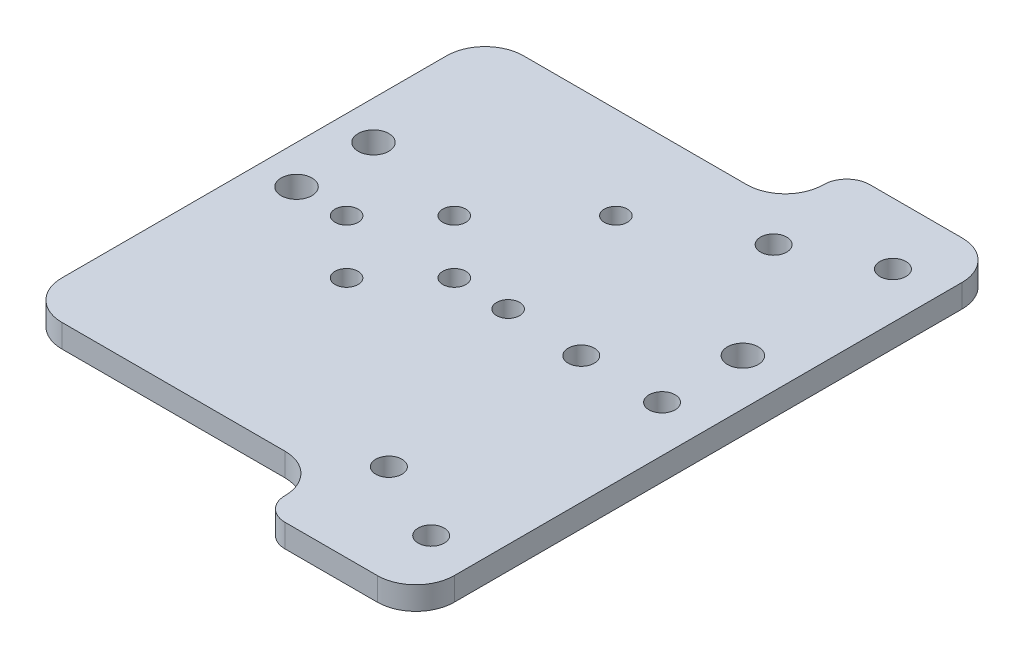
SolidWorks part; units mm, degrees
ref_plane "前视基准面" through (0, 0, 0) normal (0, 0, 1) x (1, 0, 0)
ref_plane "上视基准面" through (0, 0, 0) normal (0, 1, 0) x (1, 0, 0)
ref_plane "右视基准面" through (0, 0, 0) normal (1, 0, 0) x (0, 0, -1)
sketch "草图1" plane through (0, 0, 0) normal (0, 1, 0) x (1, 0, 0)
  line L0 (42.5, 25) -> (42.5, -25) construction
  line L5 (0, 0) -> (0, 30)
  line L6 (0, 30) -> (39, 30)
  line L7 (42.5, 0) -> (0, 0) construction
  line L8 (0, 0) -> (53, 0) construction
  line L9 (53, 30) -> (53, -30) construction
  line L10 (39, 30) -> (39, 38)
  line L11 (39, 38) -> (59, 38)
  line L12 (59, 38) -> (59, -38)
  line L13 (59, -38) -> (39, -38)
  line L14 (39, -38) -> (39, -30)
  line L15 (39, -30) -> (0, -30)
  line L16 (0, -30) -> (0, 0)
  circle A0 centre (42.5, 25) radius 1.7
  circle A1 centre (42.5, -25) radius 1.7
  circle A2 centre (42.5, 0) radius 1.7
  circle A3 centre (53, 30) radius 1.7
  circle A4 centre (53, 0) radius 1.7
  circle A5 centre (53, -30) radius 1.7
  point P0 (0, 0)
  dimension "D2" = 3.4
  dimension "D1" = 50
  dimension "D3" = 10.5
  dimension "D4" = 6
  dimension "D5" = 8
  dimension "D6" = 60
  dimension "D7" = 42.5
  dimension "D8" = 20
  dimension "D9" = 39
  dimension "D10" = 60
extrude "凸台-拉伸1" add sketch "草图1" along normal blind 3
sketch "草图2" plane through (0, 3, 0) normal (0, 1, 0) x (1, 0, 0)
  line L0 (29, 18) -> (29, 4) construction
  circle A1 centre (29, 4) radius 1.5
  circle A2 centre (29, 4) radius 1.5
  circle A3 centre (32.5, 0.5) radius 1.5
  circle A4 centre (32.5, 0.5) radius 1.5
  circle A5 centre (39.5, 7.5) radius 1.5
  circle A6 centre (39.5, 7.5) radius 1.5
  circle A7 centre (39.5, -6.5) radius 1.5
  circle A8 centre (39.5, -6.5) radius 1.5
  circle A9 centre (46.5, 0.5) radius 1.5
  circle A10 centre (46.5, 0.5) radius 1.5
  circle A11 centre (5, 0.5) radius 2
  circle A13 centre (5, 10.5) radius 2
  circle A15 centre (53, 10.5) radius 2
  circle A16 centre (53, 10.5) radius 2
  circle A17 centre (53, 0.5) radius 2
  circle A18 centre (53, 0.5) radius 2
  circle A19 centre (29, 18) radius 1.5
  circle A20 centre (29, 18) radius 1.5
  circle A21 centre (36, 11) radius 1.5
  circle A22 centre (36, 11) radius 1.5
  circle A23 centre (18.5, -6.5) radius 1.5
  circle A24 centre (11.5, 0.5) radius 1.5
  circle A25 centre (25.5, 0.5) radius 1.5
  circle A28 centre (18.5, 7.5) radius 1.5
  dimension "D1" = 0
  dimension "D2" = 0
  dimension "D3" = 0
  dimension "D4" = 0
  dimension "D5" = 0
  dimension "D8" = 0
  dimension "D9" = 0
  dimension "D10" = 0
  dimension "D11" = 0
extrude "切除-拉伸1" cut sketch "草图2" against normal through all contours A13 | A11 | A24 | A28 | A23 | A25 | A20 | A4 | A16 region at (32.5, 3, -0.5) region at (5, 3, -0.5) region at (5, 3, -10.5) region at (53, 3, -10.5) region at (29, 3, -18) region at (18.5, 3, 6.5) region at (11.5, 3, -0.5) region at (25.5, 3, -0.5) region at (18.5, 3, -7.5)
fillet "圆角1" radius 5 6 edges at (0, 1.5, 30) (0, 1.5, -30) (39, 1.5, -30) (39, 1.5, 30) (59, 1.5, 38) (59, 1.5, -38)
fillet "圆角2" radius 3 2 edges at (39, 1.5, 38) (39, 1.5, -38)
